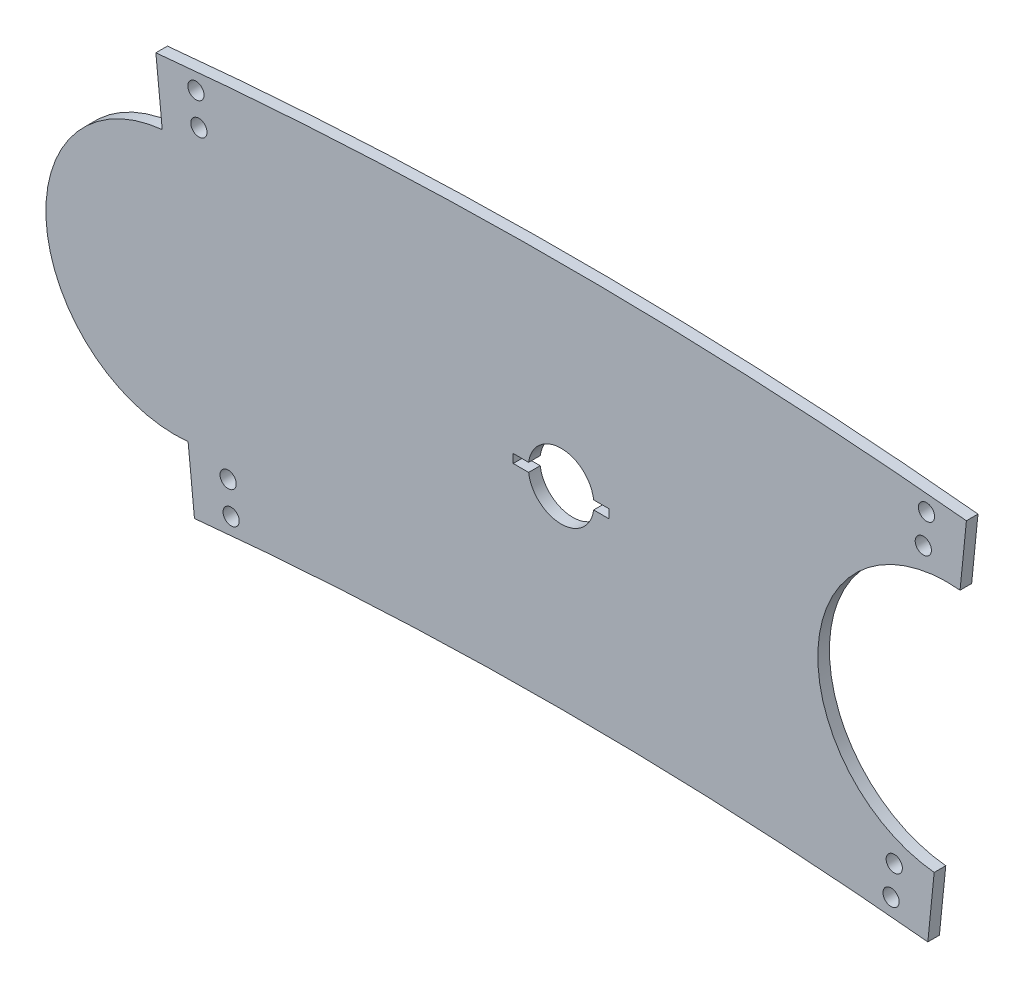
SolidWorks part; units mm, degrees
material "Balsa"
ref_plane "Front Plane" through (0, 0, 0) normal (0, 0, 1) x (1, 0, 0)
ref_plane "Top Plane" through (0, 0, 0) normal (0, 1, 0) x (1, 0, 0)
ref_plane "Right Plane" through (0, 0, 0) normal (1, 0, 0) x (0, 0, -1)
sketch "Sketch1" plane through (0, 0, 0) normal (0, 0, 1) x (1, 0, 0)
  line L0 (8.4252, 1.125) -> (12.4252, 1.125) construction
  line L1 (12.4252, 1.125) -> (12.4252, -1.125) construction
  line L2 (12.4252, -1.125) -> (8.4252, -1.125) construction
  line L3 (-8.4252, -1.125) -> (-12.4252, -1.125) construction
  line L4 (-12.4252, 1.125) -> (-8.4252, 1.125) construction
  line L5 (-12.4252, -1.125) -> (-12.4252, 1.125) construction
  line L6 (-12.4252, 1.125) -> (-8.4252, 1.125)
  line L7 (-12.4252, -1.125) -> (-12.4252, 1.125)
  line L8 (-8.4252, -1.125) -> (-12.4252, -1.125)
  line L9 (12.4252, -1.125) -> (8.4252, -1.125)
  line L10 (12.4252, 1.125) -> (12.4252, -1.125)
  line L11 (8.4252, 1.125) -> (12.4252, 1.125)
  line L12 (-105, 44.7368) -> (-103.35, 28.3195)
  line L13 (0, 0) -> (0, -1000) construction
  line L14 (0, 0) -> (192.465, 0) construction
  line L15 (105, 44.7368) -> (0, -1000) construction
  line L16 (0, -1000) -> (-105, 44.7368) construction
  line L21 (-95, -54.7619) -> (-96.65, -38.3446)
  line L22 (95, -54.7619) -> (96.65, -38.3446)
  line L23 (105, 44.7368) -> (103.35, 28.3195)
  arc A0 (-8.4252, -1.125) -> (8.4252, -1.125) centre (0, 0) ccw construction
  circle A1 centre (0, 0) radius 100 construction
  arc A3 (8.4252, 1.125) -> (-8.4252, 1.125) centre (0, 0) ccw construction
  arc A4 (8.4252, 1.125) -> (-8.4252, 1.125) centre (0, 0) ccw
  arc A5 (-8.4252, -1.125) -> (8.4252, -1.125) centre (0, 0) ccw
  arc A6 (103.35, 28.3195) -> (96.65, -38.3446) centre (100, -5.0126) ccw
  circle A8 centre (0, -1000) radius 1000 construction
  arc A9 (95, -54.7619) -> (-95, -54.7619) centre (0, -1000) ccw
  arc A10 (105, 44.7368) -> (-105, 44.7368) centre (0, -1000) ccw
  arc A11 (-103.35, 28.3195) -> (-96.65, -38.3446) centre (-100, -5.0126) ccw
  point P8 (0, 50)
  point P9 (0, -50)
  point P10 (-100, -5.0126)
  point P20 (100, -5.0126)
  point P22 (-156.6941, -31.3551)
  point P24 (-166.4707, 6.74)
  point P35 (-78.8416, -17.1247)
  point P36 (-54.9256, -17.2027)
  point P37 (0, 0)
  dimension "D1" = 200
  dimension "D2" = 2000
  dimension "D3" = 50
extrude "Boss-Extrude1" add sketch "Sketch1" along normal up to surface (3 mm away)
sketch "Sketch2" plane through (0, 0, 3) normal (0, 0, 1) x (1, 0, 0)
  circle A0 centre (86.3052, -41.5429) radius 2.1 construction
  circle A1 centre (85.4787, -49.5001) radius 2.1 construction
  circle A2 centre (94.6552, 41.5385) radius 2.1 construction
  circle A3 centre (93.8287, 33.5813) radius 2.1 construction
  circle A4 centre (-94.622, 41.4749) radius 2.1 construction
  circle A5 centre (-93.8486, 33.5124) radius 2.1 construction
  circle A6 centre (-86.272, -41.6065) radius 2.1 construction
  circle A7 centre (-85.4986, -49.569) radius 2.1 construction
  circle A8 centre (86.3052, -41.5429) radius 2.1
  circle A9 centre (85.4787, -49.5001) radius 2.1
  circle A10 centre (94.6552, 41.5385) radius 2.1
  circle A11 centre (93.8287, 33.5813) radius 2.1
  circle A12 centre (-94.622, 41.4749) radius 2.1
  circle A13 centre (-93.8486, 33.5124) radius 2.1
  circle A14 centre (-86.272, -41.6065) radius 2.1
  circle A15 centre (-85.4986, -49.569) radius 2.1
extrude "Cut-Extrude1" cut sketch "Sketch2" against normal blind 34
